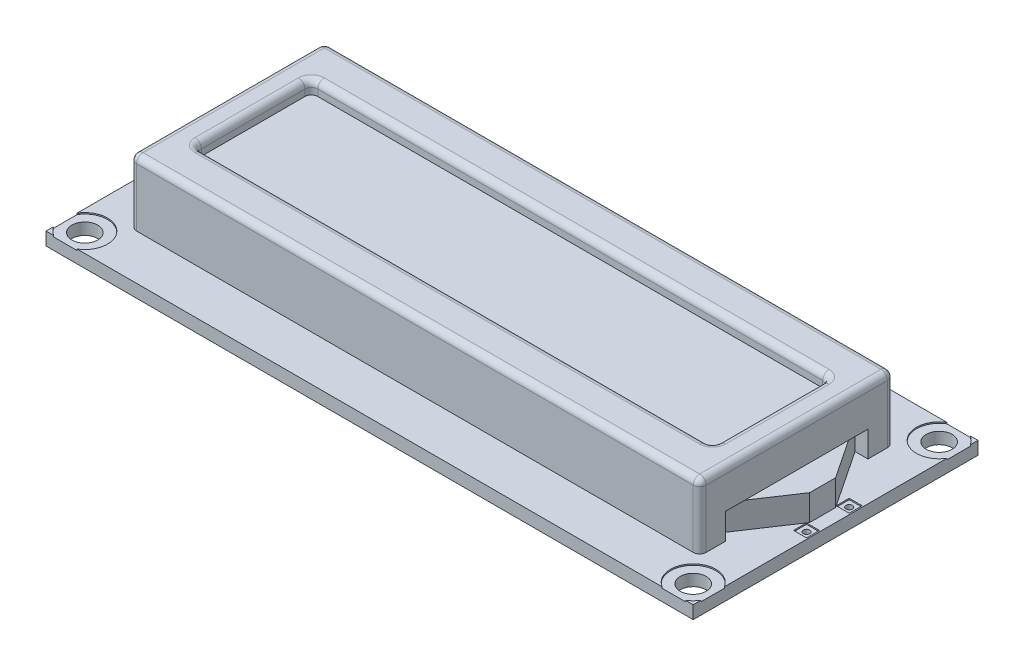
SolidWorks part; units mm, degrees
note: The reader was unsure of these and kept them because the rebuilt part matched: shared geometry of "Sketch1<3>".
ref_plane "Front Plane" through (0, 0, 0) normal (0, 0, 1) x (1, 0, 0)
ref_plane "Top Plane" through (0, 0, 0) normal (0, 1, 0) x (1, 0, 0)
ref_plane "Right Plane" through (0, 0, 0) normal (1, 0, 0) x (0, 0, -1)
sketch "Sketch1" plane through (0, 0, 0) normal (0, 1, 0) x (1, 0, 0)
  line L1 (-39.6875, -17.4625) -> (39.6875, -17.4625)
  line L2 (-39.6875, -17.4625) -> (-39.6875, 17.4625)
  line L3 (-39.6875, 17.4625) -> (39.6875, 17.4625)
  line L4 (39.6875, -17.4625) -> (39.6875, 17.4625)
  line L5 (0, 17.4625) -> (0, -17.4625) construction
  line L6 (-39.6875, 0) -> (39.6875, 0) construction
  line L7 (-34.925, -11.9062) -> (34.925, -11.9062)
  line L8 (-34.925, -11.9062) -> (-34.925, 11.9062)
  line L9 (-34.925, 11.9062) -> (34.925, 11.9062)
  line L10 (34.925, -11.9062) -> (34.925, 11.9062)
  line L11 (0, 11.9062) -> (0, -11.9062) construction
  line L12 (-34.925, 0) -> (34.925, 0) construction
  point P0 (0, 0)
  point P4 (0, 0)
  dimension "D1" = 79.375
  dimension "D2" = 34.925
  dimension "D3" = 69.85
  dimension "D4" = 23.8125
extrude "Boss-Extrude1" add sketch "Sketch1" along normal blind 1.5875 contours L7 L10 L9 L8 | L1 L4 L3 L2 L10 L7 L8 L9
extrude "Boss-Extrude2" add sketch "Sketch1<3>" along normal blind 9.525 contours L7 L10 L9 L8
sketch "Sketch1<3>" plane through (0, 0, 0) normal (0, 1, 0) x (1, 0, 0) same geometry as "Sketch1"
sketch "Sketch2" plane through (0, 1.5875, 0) normal (0, 1, 0) x (1, 0, 0)
  line L0 (-39.6875, 17.4625) -> (39.6875, 17.4625) construction
  line L2 (-39.6875, -17.4625) -> (-39.6875, 17.4625) construction
  line L3 (-39.6875, -17.4625) -> (39.6875, -17.4625) construction
  line L4 (39.6875, -17.4625) -> (39.6875, 17.4625) construction
  circle A0 centre (-37.3062, 15.0812) radius 1.5875
  circle A1 centre (-37.3062, -15.0812) radius 1.5875
  circle A2 centre (37.3062, -15.0812) radius 1.5875
  circle A3 centre (37.3062, 15.0812) radius 1.5875
  dimension "D1" = 3.175
  dimension "D2" = 2.3813
  dimension "D3" = 2.3813
  dimension "D4" = 2.3813
  dimension "D5" = 2.3813
  dimension "D6" = 2.3813
  dimension "D7" = 2.3813
  dimension "D8" = 2.3813
  dimension "D9" = 2.3813
extrude "Cut-Extrude1" cut sketch "Sketch2" against normal through all
sketch "Sketch3" plane through (0, 9.525, 0) normal (0, 1, 0) x (1, 0, 0)
  line L0 (-34.925, 11.9062) -> (34.925, 11.9062) construction
  line L1 (31.75, -7.1437) -> (-31.75, -7.1438)
  line L2 (31.75, -7.1437) -> (31.75, 7.1437)
  line L3 (31.75, 7.1437) -> (-31.75, 7.1437)
  line L4 (-31.75, -7.1438) -> (-31.75, 7.1437)
  line L5 (0, 7.1437) -> (0, -7.1438) construction
  line L6 (31.75, 0) -> (-31.75, 0) construction
  line L7 (-34.925, -11.9062) -> (-34.925, 11.9062) construction
  point P0 (0, 0)
  dimension "D1" = 4.7625
  dimension "D2" = 3.175
extrude "Cut-Extrude2" cut sketch "Sketch3" against normal blind 1.5875
fillet "Fillet1" radius 0.7937 16 edges at (-34.925, 5.5563, 11.9062) (34.925, 5.5563, 11.9062) (34.925, 5.5563, -11.9062) (-34.925, 5.5563, -11.9062) (31.75, 8.7312, 7.1437) (31.75, 8.7312, -7.1437) (-31.75, 8.7312, -7.1437) (-31.75, 8.7312, 7.1438) (-34.925, 9.525, 0) (0, 9.525, -11.9062) (34.925, 9.525, 0) (0, 9.525, 11.9062) (0, 9.525, 7.1438) (31.75, 9.525, 0) (0, 9.525, -7.1437) (-31.75, 9.525, 0)
sketch "Sketch4" plane through (0, 1.5875, 0) normal (0, 1, 0) x (1, 0, 0)
  circle A0 centre (-37.3062, 15.0812) radius 2.7781
  circle A1 centre (-37.3062, -15.0812) radius 2.7781
  circle A2 centre (37.3062, -15.0812) radius 2.7781
  circle A3 centre (37.3062, 15.0812) radius 2.7781
  dimension "D1" = 5.5562
extrude "Cut-Extrude4" cut sketch "Sketch4" against normal blind 0.1588
sketch "Sketch5" plane through (34.925, 36.5125, 0) normal (1, 0, 0) x (0, -1, 0)
  line L0 (34.925, 11.1125) -> (34.925, -11.1125) construction
  line L1 (34.925, 8.7312) -> (31.75, 8.7312)
  line L2 (34.925, 8.7312) -> (34.925, -8.7312)
  line L3 (34.925, -8.7312) -> (31.75, -8.7313)
  line L4 (31.75, 8.7312) -> (31.75, -8.7313)
  line L7 (27.7812, 11.9062) -> (34.925, 11.9062) construction
  line L8 (34.925, -11.9062) -> (27.7812, -11.9062) construction
  dimension "D1" = 3.175
  dimension "D2" = 3.175
  dimension "D3" = 3.175
extrude "Cut-Extrude5" cut sketch "Sketch5" against normal blind 1.5875 contours L4 L3 L2 L1
ref_plane "Plane1" through (38.1, 0, 0) normal (1, 0, 0) x (0, 0, -1)
sketch "Sketch6" plane through (38.1, 0, 0) normal (1, 0, 0) x (0, 0, -1)
  line L0 (8.7312, 4.7625) -> (-8.7313, 4.7625) construction
  line L1 (-1.5875, 1.5875) -> (1.5875, 1.5875)
  line L2 (-1.5875, 1.5875) -> (-1.5875, 4.7625)
  line L3 (-1.5875, 4.7625) -> (1.5875, 4.7625)
  line L4 (1.5875, 1.5875) -> (1.5875, 4.7625)
  line L5 (0, 4.7625) -> (0, 1.5875) construction
  line L6 (-1.5875, 3.175) -> (1.5875, 3.175) construction
  point P0 (0, 3.175)
  dimension "D1" = 3.175
loft "Loft1" add profiles "Sketch6" section "Sketch6" section face at (33.3375, 3.175, 0) connector at (38.1, 4.7625, 1.5875) connector at (33.3375, 4.7625, 8.7312)
sketch "Sketch7" plane through (0, 1.5875, 0) normal (0, 1, 0) x (1, 0, 0)
  line L0 (39.6875, -13.6503) -> (39.6875, 13.6503) construction
  line L1 (37.9412, 3.4131) -> (39.5287, 3.4131)
  line L2 (37.9412, 3.4131) -> (37.9412, 1.8256)
  line L3 (37.9412, 1.8256) -> (39.5287, 1.8256)
  line L4 (39.5287, 3.4131) -> (39.5287, 1.8256)
  line L5 (38.735, 1.8256) -> (38.735, 3.4131) construction
  line L6 (37.9412, 2.6194) -> (39.5287, 2.6194) construction
  line L7 (37.9412, -1.8256) -> (39.5287, -1.8256)
  line L8 (37.9412, -1.8256) -> (37.9412, -3.4131)
  line L9 (37.9412, -3.4131) -> (39.5287, -3.4131)
  line L10 (39.5287, -1.8256) -> (39.5287, -3.4131)
  line L11 (38.735, -3.4131) -> (38.735, -1.8256) construction
  line L12 (37.9412, -2.6194) -> (39.5287, -2.6194) construction
  line L13 (38.1, 1.5875) -> (34.925, 6.35) construction
  line L14 (38.1, -1.5875) -> (33.3375, -8.7312) construction
  point P0 (38.735, 2.6194)
  point P4 (38.735, -2.6194)
  dimension "D1" = 1.5875
  dimension "D2" = 1.5875
  dimension "D3" = 0.1588
extrude "Cut-Extrude6" cut sketch "Sketch7" against normal blind 0.1588
sketch "Sketch8" plane through (0, 1.4287, 0) normal (0, 1, 0) x (1, 0, 0)
  circle A0 centre (38.735, 2.6194) radius 0.3969
  circle A1 centre (38.735, -2.6194) radius 0.3969
  dimension "D1" = 0.7937
  dimension "D2" = 0.7937
extrude "Cut-Extrude7" cut sketch "Sketch8" against normal blind 1.5875
sketch "Sketch9" plane through (0, 1.5875, 0) normal (0, 1, 0) x (1, 0, 0)
  line L1 (-33.3375, 17.3038) -> (-31.75, 17.3038)
  line L2 (-33.3375, 17.3038) -> (-33.3375, 14.1288)
  line L3 (-33.3375, 14.1288) -> (-31.75, 14.1288)
  line L4 (-31.75, 17.3038) -> (-31.75, 14.1288)
  line L5 (-39.6875, -13.6503) -> (-39.6875, 13.6503) construction
  line L6 (-30.955, 17.3038) -> (-30.955, 14.1288)
  line L7 (-30.955, 14.1288) -> (-29.3675, 14.1288)
  line L8 (-29.3675, 17.3038) -> (-29.3675, 14.1288)
  line L9 (-30.955, 17.3038) -> (-29.3675, 17.3038)
  line L10 (-28.5725, 17.3038) -> (-28.5725, 14.1288)
  line L11 (-28.5725, 14.1288) -> (-26.985, 14.1288)
  line L12 (-26.985, 17.3038) -> (-26.985, 14.1288)
  line L13 (-28.5725, 17.3038) -> (-26.985, 17.3038)
  line L14 (-26.1899, 17.3038) -> (-26.1899, 14.1288)
  line L15 (-26.1899, 14.1288) -> (-24.6024, 14.1288)
  line L16 (-24.6024, 17.3038) -> (-24.6024, 14.1288)
  line L17 (-26.1899, 17.3038) -> (-24.6024, 17.3038)
  line L18 (-23.8074, 17.3038) -> (-23.8074, 14.1288)
  line L19 (-23.8074, 14.1288) -> (-22.2199, 14.1288)
  line L20 (-22.2199, 17.3038) -> (-22.2199, 14.1288)
  line L21 (-23.8074, 17.3038) -> (-22.2199, 17.3038)
  line L22 (-21.4249, 17.3038) -> (-21.4249, 14.1288)
  line L23 (-21.4249, 14.1288) -> (-19.8374, 14.1288)
  line L24 (-19.8374, 17.3038) -> (-19.8374, 14.1288)
  line L25 (-21.4249, 17.3038) -> (-19.8374, 17.3038)
  line L26 (-19.0424, 17.3038) -> (-19.0424, 14.1288)
  line L27 (-19.0424, 14.1288) -> (-17.4549, 14.1288)
  line L28 (-17.4549, 17.3038) -> (-17.4549, 14.1288)
  line L29 (-19.0424, 17.3038) -> (-17.4549, 17.3038)
  line L30 (-16.6599, 17.3038) -> (-16.6599, 14.1288)
  line L31 (-16.6599, 14.1288) -> (-15.0724, 14.1288)
  line L32 (-15.0724, 17.3038) -> (-15.0724, 14.1288)
  line L33 (-16.6599, 17.3038) -> (-15.0724, 17.3038)
  line L34 (-14.2773, 17.3038) -> (-14.2773, 14.1288)
  line L35 (-14.2773, 14.1288) -> (-12.6898, 14.1288)
  line L36 (-12.6898, 17.3038) -> (-12.6898, 14.1288)
  line L37 (-14.2773, 17.3038) -> (-12.6898, 17.3038)
  line L38 (-11.8948, 17.3038) -> (-11.8948, 14.1288)
  line L39 (-11.8948, 14.1288) -> (-10.3073, 14.1288)
  line L40 (-10.3073, 17.3038) -> (-10.3073, 14.1288)
  line L41 (-11.8948, 17.3038) -> (-10.3073, 17.3038)
  line L42 (-9.5123, 17.3038) -> (-9.5123, 14.1288)
  line L43 (-9.5123, 14.1288) -> (-7.9248, 14.1288)
  line L44 (-7.9248, 17.3038) -> (-7.9248, 14.1288)
  line L45 (-9.5123, 17.3038) -> (-7.9248, 17.3038)
  line L46 (-7.1298, 17.3038) -> (-7.1298, 14.1288)
  line L47 (-7.1298, 14.1288) -> (-5.5423, 14.1288)
  line L48 (-5.5423, 17.3038) -> (-5.5423, 14.1288)
  line L49 (-7.1298, 17.3038) -> (-5.5423, 17.3038)
  line L50 (-4.7473, 17.3038) -> (-4.7473, 14.1288)
  line L51 (-4.7473, 14.1288) -> (-3.1598, 14.1288)
  line L52 (-3.1598, 17.3038) -> (-3.1598, 14.1288)
  line L53 (-4.7473, 17.3038) -> (-3.1598, 17.3038)
  line L54 (-2.3647, 17.3038) -> (-2.3647, 14.1288)
  line L55 (-2.3647, 14.1288) -> (-0.7772, 14.1288)
  line L56 (-0.7772, 17.3038) -> (-0.7772, 14.1288)
  line L57 (-2.3647, 17.3038) -> (-0.7772, 17.3038)
  line L58 (0.0178, 17.3038) -> (0.0178, 14.1288)
  line L59 (0.0178, 14.1288) -> (1.6053, 14.1288)
  line L60 (1.6053, 17.3038) -> (1.6053, 14.1288)
  line L61 (0.0178, 17.3038) -> (1.6053, 17.3038)
  line L62 (2.4003, 17.3038) -> (2.4003, 14.1288)
  line L63 (2.4003, 14.1288) -> (3.9878, 14.1288)
  line L64 (3.9878, 17.3038) -> (3.9878, 14.1288)
  line L65 (2.4003, 17.3038) -> (3.9878, 17.3038)
  line L66 (-35.8753, 17.4625) -> (35.8753, 17.4625) construction
  dimension "D1" = 6.35
  dimension "D2" = 1.5875
  dimension "D3" = 3.175
  dimension "D5" = 0.1588
  dimension "D4" = 16
extrude "Boss-Extrude4" add sketch "Sketch9" along normal blind 0.7937
fillet "Fillet2" radius 0.5953 64 edges at (3.9878, 2.3812, -15.7163) (3.194, 2.3812, -14.1288) (2.4003, 2.3812, -15.7163) (3.194, 2.3812, -17.3038) (1.6053, 2.3812, -15.7163) (0.8115, 2.3812, -14.1288) (0.0178, 2.3812, -15.7163) (0.8115, 2.3812, -17.3038) (-0.7772, 2.3812, -15.7163) (-1.571, 2.3812, -14.1288) (-2.3647, 2.3812, -15.7163) (-1.571, 2.3812, -17.3038) (-3.1598, 2.3812, -15.7163) (-3.9535, 2.3812, -14.1288) (-4.7473, 2.3812, -15.7163) (-3.9535, 2.3812, -17.3038) (-5.5423, 2.3812, -15.7163) (-6.336, 2.3812, -14.1288) (-7.1298, 2.3812, -15.7163) (-6.336, 2.3812, -17.3038) (-7.9248, 2.3812, -15.7163) (-8.7186, 2.3812, -14.1288) (-9.5123, 2.3812, -15.7163) (-8.7186, 2.3812, -17.3038) (-10.3073, 2.3812, -15.7163) (-11.1011, 2.3812, -14.1288) (-11.8948, 2.3812, -15.7163) (-11.1011, 2.3812, -17.3038) (-12.6898, 2.3812, -15.7163) (-13.4836, 2.3812, -14.1288) (-14.2773, 2.3812, -15.7163) (-13.4836, 2.3812, -17.3038) (-15.0724, 2.3812, -15.7163) (-15.8661, 2.3812, -14.1288) (-16.6599, 2.3812, -15.7163) (-15.8661, 2.3812, -17.3038) (-17.4549, 2.3812, -15.7163) (-18.2486, 2.3812, -14.1288) (-19.0424, 2.3812, -15.7163) (-18.2486, 2.3812, -17.3038) (-19.8374, 2.3812, -15.7163) (-20.6312, 2.3812, -14.1288) (-21.4249, 2.3812, -15.7163) (-20.6312, 2.3812, -17.3038) (-22.2199, 2.3812, -15.7163) (-23.0137, 2.3812, -14.1288) (-23.8074, 2.3812, -15.7163) (-23.0137, 2.3812, -17.3038) (-24.6024, 2.3812, -15.7163) (-25.3962, 2.3812, -14.1288) (-26.1899, 2.3812, -15.7163) (-25.3962, 2.3812, -17.3038) (-26.985, 2.3812, -15.7163) (-27.7787, 2.3812, -14.1288) (-28.5725, 2.3812, -15.7163) (-27.7787, 2.3812, -17.3038) (-29.3675, 2.3812, -15.7163) (-30.1612, 2.3812, -14.1288) (-30.955, 2.3812, -15.7163) (-30.1612, 2.3812, -17.3038) (-32.5437, 2.3812, -17.3038) (-31.75, 2.3812, -15.7163) (-32.5437, 2.3812, -14.1288) (-33.3375, 2.3812, -15.7163)
sketch "Sketch10" plane through (0, 0, 0) normal (0, -1, 0) x (1, 0, 0)
  line L1 (-33.02, -17.3038) -> (-31.2737, -17.3038)
  line L2 (-33.3375, -16.9863) -> (-33.3375, -15.24)
  line L3 (-33.02, -14.9225) -> (-31.2737, -14.9225)
  line L4 (-30.9562, -16.9863) -> (-30.9562, -15.24)
  line L5 (-39.6875, 17.4625) -> (-39.6875, -17.4625) construction
  line L6 (-30.6375, -14.9225) -> (-28.8912, -14.9225)
  line L7 (-28.5737, -16.9863) -> (-28.5737, -15.24)
  line L8 (-30.6375, -17.3038) -> (-28.8912, -17.3038)
  line L9 (-30.955, -16.9863) -> (-30.955, -15.24)
  line L10 (-28.255, -14.9225) -> (-26.5087, -14.9225)
  line L11 (-26.1912, -16.9863) -> (-26.1912, -15.24)
  line L12 (-28.255, -17.3038) -> (-26.5087, -17.3038)
  line L13 (-28.5725, -16.9863) -> (-28.5725, -15.24)
  line L14 (-25.8724, -14.9225) -> (-24.1262, -14.9225)
  line L15 (-23.8087, -16.9863) -> (-23.8087, -15.24)
  line L16 (-25.8724, -17.3038) -> (-24.1262, -17.3038)
  line L17 (-26.1899, -16.9863) -> (-26.1899, -15.24)
  line L18 (-23.4899, -14.9225) -> (-21.7437, -14.9225)
  line L19 (-21.4262, -16.9863) -> (-21.4262, -15.24)
  line L20 (-23.4899, -17.3038) -> (-21.7437, -17.3038)
  line L21 (-23.8074, -16.9863) -> (-23.8074, -15.24)
  line L22 (-21.1074, -14.9225) -> (-19.3612, -14.9225)
  line L23 (-19.0437, -16.9863) -> (-19.0437, -15.24)
  line L24 (-21.1074, -17.3038) -> (-19.3612, -17.3038)
  line L25 (-21.4249, -16.9863) -> (-21.4249, -15.24)
  line L26 (-18.7249, -14.9225) -> (-16.9786, -14.9225)
  line L27 (-16.6611, -16.9863) -> (-16.6611, -15.24)
  line L28 (-18.7249, -17.3038) -> (-16.9786, -17.3038)
  line L29 (-19.0424, -16.9863) -> (-19.0424, -15.24)
  line L30 (-16.3424, -14.9225) -> (-14.5961, -14.9225)
  line L31 (-14.2786, -16.9863) -> (-14.2786, -15.24)
  line L32 (-16.3424, -17.3038) -> (-14.5961, -17.3038)
  line L33 (-16.6599, -16.9863) -> (-16.6599, -15.24)
  line L34 (-13.9598, -14.9225) -> (-12.2136, -14.9225)
  line L35 (-11.8961, -16.9863) -> (-11.8961, -15.24)
  line L36 (-13.9598, -17.3038) -> (-12.2136, -17.3038)
  line L37 (-14.2773, -16.9863) -> (-14.2773, -15.24)
  line L38 (-11.5773, -14.9225) -> (-9.8311, -14.9225)
  line L39 (-9.5136, -16.9863) -> (-9.5136, -15.24)
  line L40 (-11.5773, -17.3038) -> (-9.8311, -17.3038)
  line L41 (-11.8948, -16.9863) -> (-11.8948, -15.24)
  line L42 (-9.1948, -14.9225) -> (-7.4486, -14.9225)
  line L43 (-7.1311, -16.9863) -> (-7.1311, -15.24)
  line L44 (-9.1948, -17.3038) -> (-7.4486, -17.3038)
  line L45 (-9.5123, -16.9863) -> (-9.5123, -15.24)
  line L46 (-6.8123, -14.9225) -> (-5.066, -14.9225)
  line L47 (-4.7485, -16.9863) -> (-4.7485, -15.24)
  line L48 (-6.8123, -17.3038) -> (-5.066, -17.3038)
  line L49 (-7.1298, -16.9863) -> (-7.1298, -15.24)
  line L50 (-4.4298, -14.9225) -> (-2.6835, -14.9225)
  line L51 (-2.366, -16.9863) -> (-2.366, -15.24)
  line L52 (-4.4298, -17.3038) -> (-2.6835, -17.3038)
  line L53 (-4.7473, -16.9863) -> (-4.7473, -15.24)
  line L54 (-2.0472, -14.9225) -> (-0.301, -14.9225)
  line L55 (0.0165, -16.9863) -> (0.0165, -15.24)
  line L56 (-2.0472, -17.3038) -> (-0.301, -17.3038)
  line L57 (-2.3647, -16.9863) -> (-2.3647, -15.24)
  line L58 (0.3353, -14.9225) -> (2.0815, -14.9225)
  line L59 (2.399, -16.9863) -> (2.399, -15.24)
  line L60 (0.3353, -17.3038) -> (2.0815, -17.3038)
  line L61 (0.0178, -16.9863) -> (0.0178, -15.24)
  line L62 (2.7178, -14.9225) -> (4.464, -14.9225)
  line L63 (4.7815, -16.9863) -> (4.7815, -15.24)
  line L64 (2.7178, -17.3038) -> (4.464, -17.3038)
  line L65 (2.4003, -16.9863) -> (2.4003, -15.24)
  line L66 (-39.6875, -17.4625) -> (39.6875, -17.4625) construction
  arc A0 (-31.2737, -17.3038) -> (-30.9562, -16.9863) centre (-31.2737, -16.9863) ccw
  arc A1 (-33.02, -17.3038) -> (-33.3375, -16.9863) centre (-33.02, -16.9863) cw
  arc A2 (-31.2737, -14.9225) -> (-30.9562, -15.24) centre (-31.2737, -15.24) cw
  arc A3 (-33.3375, -15.24) -> (-33.02, -14.9225) centre (-33.02, -15.24) cw
  arc A4 (-30.955, -15.24) -> (-30.6375, -14.9225) centre (-30.6375, -15.24) cw
  arc A5 (-28.8912, -14.9225) -> (-28.5737, -15.24) centre (-28.8912, -15.24) cw
  arc A6 (-28.8912, -17.3038) -> (-28.5737, -16.9863) centre (-28.8912, -16.9863) ccw
  arc A7 (-30.6375, -17.3038) -> (-30.955, -16.9863) centre (-30.6375, -16.9863) cw
  arc A8 (-28.5725, -15.24) -> (-28.255, -14.9225) centre (-28.255, -15.24) cw
  arc A9 (-26.5087, -14.9225) -> (-26.1912, -15.24) centre (-26.5087, -15.24) cw
  arc A10 (-26.5087, -17.3038) -> (-26.1912, -16.9863) centre (-26.5087, -16.9863) ccw
  arc A11 (-28.255, -17.3038) -> (-28.5725, -16.9863) centre (-28.255, -16.9863) cw
  arc A12 (-26.1899, -15.24) -> (-25.8724, -14.9225) centre (-25.8724, -15.24) cw
  arc A13 (-24.1262, -14.9225) -> (-23.8087, -15.24) centre (-24.1262, -15.24) cw
  arc A14 (-24.1262, -17.3038) -> (-23.8087, -16.9863) centre (-24.1262, -16.9863) ccw
  arc A15 (-25.8724, -17.3038) -> (-26.1899, -16.9863) centre (-25.8724, -16.9863) cw
  arc A16 (-23.8074, -15.24) -> (-23.4899, -14.9225) centre (-23.4899, -15.24) cw
  arc A17 (-21.7437, -14.9225) -> (-21.4262, -15.24) centre (-21.7437, -15.24) cw
  arc A18 (-21.7437, -17.3038) -> (-21.4262, -16.9863) centre (-21.7437, -16.9863) ccw
  arc A19 (-23.4899, -17.3038) -> (-23.8074, -16.9863) centre (-23.4899, -16.9863) cw
  arc A20 (-21.4249, -15.24) -> (-21.1074, -14.9225) centre (-21.1074, -15.24) cw
  arc A21 (-19.3612, -14.9225) -> (-19.0437, -15.24) centre (-19.3612, -15.24) cw
  arc A22 (-19.3612, -17.3038) -> (-19.0437, -16.9863) centre (-19.3612, -16.9863) ccw
  arc A23 (-21.1074, -17.3038) -> (-21.4249, -16.9863) centre (-21.1074, -16.9863) cw
  arc A24 (-19.0424, -15.24) -> (-18.7249, -14.9225) centre (-18.7249, -15.24) cw
  arc A25 (-16.9786, -14.9225) -> (-16.6611, -15.24) centre (-16.9786, -15.24) cw
  arc A26 (-16.9786, -17.3038) -> (-16.6611, -16.9863) centre (-16.9786, -16.9863) ccw
  arc A27 (-18.7249, -17.3038) -> (-19.0424, -16.9863) centre (-18.7249, -16.9863) cw
  arc A28 (-16.6599, -15.24) -> (-16.3424, -14.9225) centre (-16.3424, -15.24) cw
  arc A29 (-14.5961, -14.9225) -> (-14.2786, -15.24) centre (-14.5961, -15.24) cw
  arc A30 (-14.5961, -17.3038) -> (-14.2786, -16.9863) centre (-14.5961, -16.9863) ccw
  arc A31 (-16.3424, -17.3038) -> (-16.6599, -16.9863) centre (-16.3424, -16.9863) cw
  arc A32 (-14.2773, -15.24) -> (-13.9598, -14.9225) centre (-13.9598, -15.24) cw
  arc A33 (-12.2136, -14.9225) -> (-11.8961, -15.24) centre (-12.2136, -15.24) cw
  arc A34 (-12.2136, -17.3038) -> (-11.8961, -16.9863) centre (-12.2136, -16.9863) ccw
  arc A35 (-13.9598, -17.3038) -> (-14.2773, -16.9863) centre (-13.9598, -16.9863) cw
  arc A36 (-11.8948, -15.24) -> (-11.5773, -14.9225) centre (-11.5773, -15.24) cw
  arc A37 (-9.8311, -14.9225) -> (-9.5136, -15.24) centre (-9.8311, -15.24) cw
  arc A38 (-9.8311, -17.3038) -> (-9.5136, -16.9863) centre (-9.8311, -16.9863) ccw
  arc A39 (-11.5773, -17.3038) -> (-11.8948, -16.9863) centre (-11.5773, -16.9863) cw
  arc A40 (-9.5123, -15.24) -> (-9.1948, -14.9225) centre (-9.1948, -15.24) cw
  arc A41 (-7.4486, -14.9225) -> (-7.1311, -15.24) centre (-7.4486, -15.24) cw
  arc A42 (-7.4486, -17.3038) -> (-7.1311, -16.9863) centre (-7.4486, -16.9863) ccw
  arc A43 (-9.1948, -17.3038) -> (-9.5123, -16.9863) centre (-9.1948, -16.9863) cw
  arc A44 (-7.1298, -15.24) -> (-6.8123, -14.9225) centre (-6.8123, -15.24) cw
  arc A45 (-5.066, -14.9225) -> (-4.7485, -15.24) centre (-5.066, -15.24) cw
  arc A46 (-5.066, -17.3038) -> (-4.7485, -16.9863) centre (-5.066, -16.9863) ccw
  arc A47 (-6.8123, -17.3038) -> (-7.1298, -16.9863) centre (-6.8123, -16.9863) cw
  arc A48 (-4.7473, -15.24) -> (-4.4298, -14.9225) centre (-4.4298, -15.24) cw
  arc A49 (-2.6835, -14.9225) -> (-2.366, -15.24) centre (-2.6835, -15.24) cw
  arc A50 (-2.6835, -17.3038) -> (-2.366, -16.9863) centre (-2.6835, -16.9863) ccw
  arc A51 (-4.4298, -17.3038) -> (-4.7473, -16.9863) centre (-4.4298, -16.9863) cw
  arc A52 (-2.3647, -15.24) -> (-2.0472, -14.9225) centre (-2.0472, -15.24) cw
  arc A53 (-0.301, -14.9225) -> (0.0165, -15.24) centre (-0.301, -15.24) cw
  arc A54 (-0.301, -17.3038) -> (0.0165, -16.9863) centre (-0.301, -16.9863) ccw
  arc A55 (-2.0472, -17.3038) -> (-2.3647, -16.9863) centre (-2.0472, -16.9863) cw
  arc A56 (0.0178, -15.24) -> (0.3353, -14.9225) centre (0.3353, -15.24) cw
  arc A57 (2.0815, -14.9225) -> (2.399, -15.24) centre (2.0815, -15.24) cw
  arc A58 (2.0815, -17.3038) -> (2.399, -16.9863) centre (2.0815, -16.9863) ccw
  arc A59 (0.3353, -17.3038) -> (0.0178, -16.9863) centre (0.3353, -16.9863) cw
  arc A60 (2.4003, -15.24) -> (2.7178, -14.9225) centre (2.7178, -15.24) cw
  arc A61 (4.464, -14.9225) -> (4.7815, -15.24) centre (4.464, -15.24) cw
  arc A62 (4.464, -17.3038) -> (4.7815, -16.9863) centre (4.464, -16.9863) ccw
  arc A63 (2.7178, -17.3038) -> (2.4003, -16.9863) centre (2.7178, -16.9863) cw
  point P13 (-30.9562, -17.3038)
  point P16 (-33.3375, -17.3038)
  point P19 (-30.9562, -14.9225)
  point P22 (-33.3375, -14.9225)
  dimension "D4" = 0.3175
  dimension "D1" = 6.35
  dimension "D2" = 2.3813
  dimension "D3" = 2.3813
  dimension "D6" = 0.1588
  dimension "D5" = 16
extrude "Boss-Extrude5" add sketch "Sketch10" along normal blind 2.3813
sketch "Sketch11" plane through (0, -2.3813, 0) normal (0, -1, 0) x (1, 0, 0)
  line L0 (0.8115, -15.7045) -> (1.6053, -15.7045)
  line L1 (3.194, -15.7045) -> (3.9878, -15.7045)
  line L2 (3.194, -15.7045) -> (3.194, -16.5217)
  line L3 (3.194, -16.5217) -> (3.9878, -16.5217)
  line L4 (3.9878, -15.7045) -> (3.9878, -16.5217)
  line L5 (3.5909, -16.5217) -> (3.5909, -15.7045) construction
  line L6 (3.194, -16.1131) -> (3.9878, -16.1131) construction
  line L7 (0.8115, -15.7045) -> (0.8115, -16.5217)
  line L8 (0.8115, -16.5217) -> (1.6053, -16.5217)
  line L9 (1.6053, -15.7045) -> (1.6053, -16.5217)
  line L10 (-1.571, -15.7045) -> (-0.7772, -15.7045)
  line L11 (-1.571, -15.7045) -> (-1.571, -16.5217)
  line L12 (-1.571, -16.5217) -> (-0.7772, -16.5217)
  line L13 (-0.7772, -15.7045) -> (-0.7772, -16.5217)
  line L14 (-3.9535, -15.7045) -> (-3.1598, -15.7045)
  line L15 (-3.9535, -15.7045) -> (-3.9535, -16.5217)
  line L16 (-3.9535, -16.5217) -> (-3.1598, -16.5217)
  line L17 (-3.1598, -15.7045) -> (-3.1598, -16.5217)
  line L18 (-6.336, -15.7045) -> (-5.5423, -15.7045)
  line L19 (-6.336, -15.7045) -> (-6.336, -16.5217)
  line L20 (-6.336, -16.5217) -> (-5.5423, -16.5217)
  line L21 (-5.5423, -15.7045) -> (-5.5423, -16.5217)
  line L22 (-8.7186, -15.7045) -> (-7.9248, -15.7045)
  line L23 (-8.7186, -15.7045) -> (-8.7186, -16.5217)
  line L24 (-8.7186, -16.5217) -> (-7.9248, -16.5217)
  line L25 (-7.9248, -15.7045) -> (-7.9248, -16.5217)
  line L26 (-11.1011, -15.7045) -> (-10.3073, -15.7045)
  line L27 (-11.1011, -15.7045) -> (-11.1011, -16.5217)
  line L28 (-11.1011, -16.5217) -> (-10.3073, -16.5217)
  line L29 (-10.3073, -15.7045) -> (-10.3073, -16.5217)
  line L30 (-13.4836, -15.7045) -> (-12.6898, -15.7045)
  line L31 (-13.4836, -15.7045) -> (-13.4836, -16.5217)
  line L32 (-13.4836, -16.5217) -> (-12.6898, -16.5217)
  line L33 (-12.6898, -15.7045) -> (-12.6898, -16.5217)
  line L34 (-15.8661, -15.7045) -> (-15.0724, -15.7045)
  line L35 (-15.8661, -15.7045) -> (-15.8661, -16.5217)
  line L36 (-15.8661, -16.5217) -> (-15.0724, -16.5217)
  line L37 (-15.0724, -15.7045) -> (-15.0724, -16.5217)
  line L38 (-18.2486, -15.7045) -> (-17.4549, -15.7045)
  line L39 (-18.2486, -15.7045) -> (-18.2486, -16.5217)
  line L40 (-18.2486, -16.5217) -> (-17.4549, -16.5217)
  line L41 (-17.4549, -15.7045) -> (-17.4549, -16.5217)
  line L42 (-20.6312, -15.7045) -> (-19.8374, -15.7045)
  line L43 (-20.6312, -15.7045) -> (-20.6312, -16.5217)
  line L44 (-20.6312, -16.5217) -> (-19.8374, -16.5217)
  line L45 (-19.8374, -15.7045) -> (-19.8374, -16.5217)
  line L46 (-23.0137, -15.7045) -> (-22.2199, -15.7045)
  line L47 (-23.0137, -15.7045) -> (-23.0137, -16.5217)
  line L48 (-23.0137, -16.5217) -> (-22.2199, -16.5217)
  line L49 (-22.2199, -15.7045) -> (-22.2199, -16.5217)
  line L50 (-25.3962, -15.7045) -> (-24.6024, -15.7045)
  line L51 (-25.3962, -15.7045) -> (-25.3962, -16.5217)
  line L52 (-25.3962, -16.5217) -> (-24.6024, -16.5217)
  line L53 (-24.6024, -15.7045) -> (-24.6024, -16.5217)
  line L54 (-27.7787, -15.7045) -> (-26.985, -15.7045)
  line L55 (-27.7787, -15.7045) -> (-27.7787, -16.5217)
  line L56 (-27.7787, -16.5217) -> (-26.985, -16.5217)
  line L57 (-26.985, -15.7045) -> (-26.985, -16.5217)
  line L58 (-30.1612, -15.7045) -> (-29.3675, -15.7045)
  line L59 (-30.1612, -15.7045) -> (-30.1612, -16.5217)
  line L60 (-30.1612, -16.5217) -> (-29.3675, -16.5217)
  line L61 (-29.3675, -15.7045) -> (-29.3675, -16.5217)
  line L62 (-32.5438, -15.7045) -> (-31.75, -15.7045)
  line L63 (-32.5438, -15.7045) -> (-32.5438, -16.5217)
  line L64 (-32.5438, -16.5217) -> (-31.75, -16.5217)
  line L65 (-31.75, -15.7045) -> (-31.75, -16.5217)
  point P0 (3.5909, -16.1131)
  dimension "D1" = 0.7937
  dimension "D2" = 16
extrude "Boss-Extrude6" add sketch "Sketch11" along normal blind 6.35
